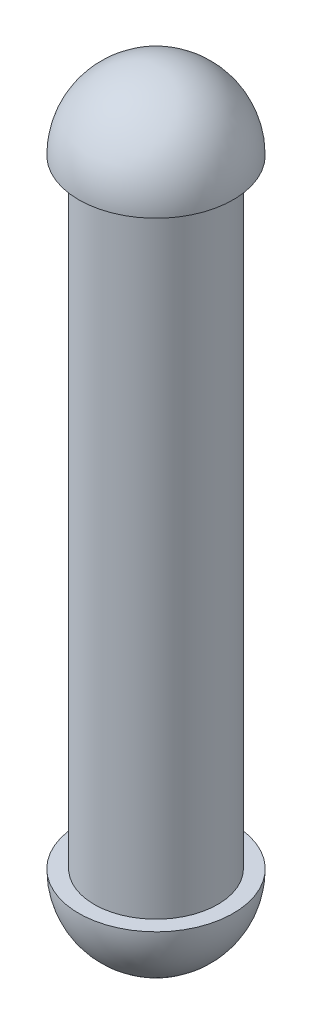
SolidWorks part; units mm, degrees
material "1.4000 (X6Cr13)"
ref_plane "Płaszczyzna przednia" through (0, 0, 0) normal (0, 0, 1) x (1, 0, 0)
ref_plane "Płaszczyzna górna" through (0, 0, 0) normal (0, 1, 0) x (1, 0, 0)
ref_plane "Płaszczyzna prawa" through (0, 0, 0) normal (1, 0, 0) x (0, 0, -1)
sketch "Szkic1" plane through (0, 0, 0) normal (0, 1, 0) x (1, 0, 0)
  circle A0 centre (0, 0) radius 4
extrude "Dodanie-wyciągnięcie1" add sketch "Szkic1" along normal blind 40
sketch "Szkic2" plane through (0, 40, 0) normal (0, 1, 0) x (1, 0, 0)
  circle A0 centre (0, 0) radius 5
extrude "Dodanie-wyciągnięcie2" add sketch "Szkic2" along normal blind 5
fillet "Zaokrąglenie1" radius 5 1 edges at (0, 45, 5)
sketch "Szkic3" plane through (0, 0, 0) normal (0, -1, 0) x (1, 0, 0)
  circle A0 centre (0, 0) radius 5
extrude "Dodanie-wyciągnięcie3" add sketch "Szkic3" along normal blind 5
fillet "Zaokrąglenie2" radius 5 1 edges at (0, -5, -5)
